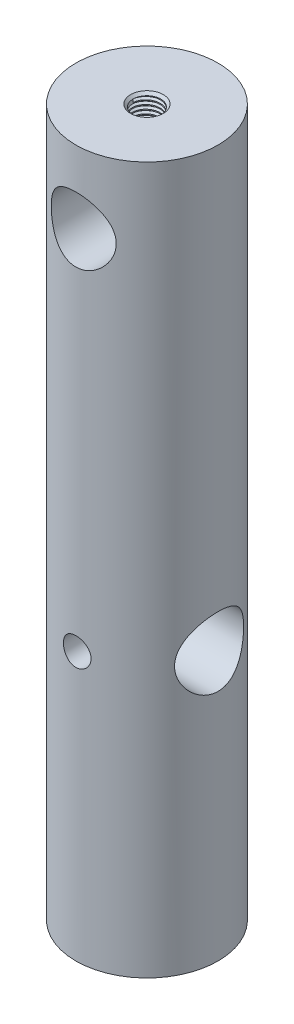
SolidWorks part; units mm, degrees
material "AISI 1020"
ref_plane "Plano superior" through (0, 0, 0) normal (0, 0, 1) x (1, 0, 0)
ref_plane "Plano frontal" through (0, 0, 0) normal (0, 1, 0) x (1, 0, 0)
ref_plane "Plano direito" through (0, 0, 0) normal (1, 0, 0) x (0, 0, -1)
sketch "Esboço1" plane through (0, 0, 0) normal (0, 1, 0) x (1, 0, 0)
  circle A0 centre (0, 0) radius 17.5
  dimension "D1" = 35
extrude "Ressalto-extrusão1" add sketch "Esboço1" along normal blind 174
sketch "Esboço3" plane through (0, 0, 0) normal (1, 0, 0) x (0, 0, -1)
  line L0 (0, 0) -> (0, 80.9795) construction
  circle A0 centre (0, 66) radius 8.5
  dimension "D1" = 17
  dimension "D2" = 66
extrude "Corte-extrusão1" cut sketch "Esboço3" against normal mid plane 172
hole_wizard "Furo roscado de M82" positions "Esboço14" profile "Esboço15" tap size "M8" standard "DIN" end condition up to next
sketch "Esboço14" plane through (0, 0, 0) normal (0, 0, 1) x (1, 0, 0)
  line L0 (0, 0) -> (0, 84.0379) construction
  line L2 (17.5, 74.5) -> (-17.5, 74.5) construction
  line L3 (-17.5, 57.5) -> (17.5, 57.5) construction
  line L4 (17.5, 74.5) -> (-17.5, 74.5) construction
  line L5 (-17.5, 57.5) -> (17.5, 57.5) construction
  line L6 (-17.5, 74.5) -> (17.5, 57.5) construction
  point P0 (0, 66)
cosmetic thread "Rosca de furo1" parameters "D2"=8
sketch "Esboço15" plane through (0, 66, 0) normal (1, 0, 0) x (0, 1, 0)
  line L0 (0, 0) -> (0, 17.5)
  line L1 (0, 17.5) -> (3.4, 17.5)
  line L2 (3.4, 17.5) -> (3.4, 0)
  line L5 (3.4, 0) -> (0, 0)
  line L11 (0, -6.35) -> (0, 107.95) construction
  dimension "Thru Tap Drill Dia." = 6.8
  dimension "Thru Tap Drill Depth" = 17.5
sketch "Esboço8" plane through (0, 0, 0) normal (0, 0, 1) x (1, 0, 0)
  line L0 (17.5, 174) -> (-17.5, 174) construction
  circle A0 centre (0, 156) radius 8
  dimension "D1" = 16
  dimension "D2" = 18
extrude "Corte-extrusão4" cut sketch "Esboço8" against normal mid plane 172
hole_wizard "Furo roscado de M81" positions "Esboço12" profile "Esboço13" tap size "M8" standard "DIN" end condition up to next
sketch "Esboço12" plane through (0, 174, 0) normal (0, 1, 0) x (1, 0, 0)
  point P0 (0, 0)
  point P4 (0, 0)
sketch "Esboço13" plane through (0, 174, 0) normal (1, 0, 0) x (0, 0, 1)
  line L0 (0, 0) -> (0, 99.5)
  line L1 (0, 99.5) -> (3.4, 99.5)
  line L2 (3.4, 99.5) -> (3.4, 0.625)
  line L3 (3.4, 0.625) -> (4.025, 0)
  line L5 (4.025, 0) -> (0, 0)
  line L6 (-3.4, 0.625) -> (-4.025, 0) construction
  line L11 (0, -6.35) -> (0, 107.95) construction
  dimension "Thru Tap Drill Dia." = 6.8
  dimension "Thru Tap Drill Depth" = 99.5
  dimension "Near C'Sink Dia." = 8.05
  dimension "Near C'Sink Angle" = 90
cosmetic thread "Rosca de furo2" parameters "D2"=8
cosmetic thread "Rosca de furo3" parameters "D2"=8
thread "Rosca1" pitch 1 method cut profile "Perfil da rosca1" start angle 0, offset 0, length 0, pitch 1, diameter 6.8
ref_plane "Plano1" through (-3.4, 173.375, 0) normal (0, 0, 1) x (-1, 0, 0)
sketch "Perfil da rosca1" plane through (-3.4, 173.375, 0) normal (0, 0, 1) x (-1, 0, 0)
  line L0 (0, 0) -> (0, 1) construction
  line L1 (0, 0) -> (0.5413, 0.3125)
  line L2 (0.5413, 0.3125) -> (0.5413, 0.4375)
  line L3 (0.5413, 0.4375) -> (0, 0.75)
  line L4 (0.5413, 0.375) -> (0, 0.375) construction
  line L11 (0, 0) -> (0, 0.75)
  point P2 (0, 0)
  dimension "Pitch" = 1
  dimension "Profile_Angle" = 60
  dimension "Profile_Land" = 0.125
  dimension "Profile_Height" = 0.5413
ref_plane "Plano2" through (-17.5, 0, 0) normal (-1, 0, 0) x (0, 0, 1)
ref_plane "Plano3" through (17.5, 0, 0) normal (1, 0, 0) x (0, 0, -1)
